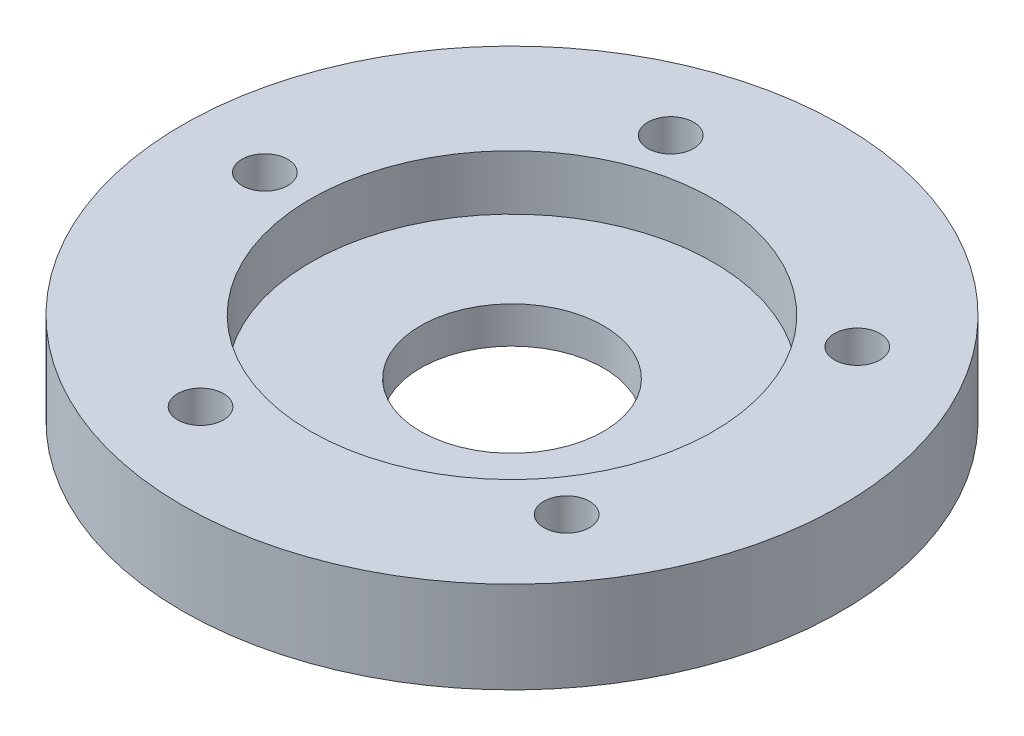
SolidWorks part; units mm, degrees
ref_plane "Front Plane" through (0, 0, 0) normal (0, 0, 1) x (1, 0, 0)
ref_plane "Top Plane" through (0, 0, 0) normal (0, 1, 0) x (1, 0, 0)
ref_plane "Right Plane" through (0, 0, 0) normal (1, 0, 0) x (0, 0, -1)
sketch "Sketch1" plane through (0, 0, 0) normal (0, 1, 0) x (1, 0, 0)
  line L0 (-13.5, 0) -> (13.5, 0) construction
  circle A0 centre (0, 0) radius 16
  circle A1 centre (0, 0) radius 13.5
  circle A2 centre (0, 0) radius 1.75
  circle A3 centre (-13.5, 0) radius 1.25
  circle A4 centre (-4.1717, 12.8393) radius 1.25
  circle A5 centre (10.9217, 7.9351) radius 1.25
  circle A6 centre (10.9217, -7.9351) radius 1.25
  circle A7 centre (-4.1717, -12.8393) radius 1.25
  point P19 (0, 0)
  dimension "D1" = 32
  dimension "D2" = 2.5
  dimension "D3" = 3.5
  dimension "D4" = 2.5
  dimension "D5" = 5
extrude "Boss-Extrude1" add sketch "Sketch1" along normal blind 2 and the other way blind 3 contours A0 A7 A1 A3 A4 A5 A6 | L0 A3 A1 A7 A6 A2 | A3 L0 A2 A1 A5 A4 region at (0, 0, -5.7653) region at (0, 0, 5.7653) region at (-15.5475, 0, 0)
sketch "Sketch2" plane through (0, 2, 0) normal (0, 1, 0) x (1, 0, 0)
  circle A0 centre (0, 0) radius 2.95
  circle A1 centre (0, 0) radius 4.95
  dimension "D1" = 5.9
  dimension "D2" = 2
extrude "Boss-Extrude3" add sketch "Sketch2" along normal blind 3 contours A1 A0 region at (-4.81, 2, 0)
sketch "Sketch4" plane through (0, 2, 0) normal (0, 1, 0) x (1, 0, 0)
  circle A0 centre (0, 0) radius 2
sketch "Sketch5" plane through (0, -3, 0) normal (0, -1, 0) x (1, 0, 0)
  circle A0 centre (0, 0) radius 3.5
  dimension "D1" = 7
extrude "Cut-Extrude2" cut sketch "Sketch5" against normal blind 4
sketch "Sketch6" plane through (0, 2, 0) normal (0, 1, 0) x (1, 0, 0)
  circle A0 centre (0, 0) radius 16
  circle A1 centre (0, 0) radius 18
  dimension "D1" = 2
extrude "Boss-Extrude4" add sketch "Sketch6" against normal blind 5
sketch "Sketch7" plane through (0, 2, 0) normal (0, 1, 0) x (1, 0, 0)
  circle A0 centre (0, 0) radius 11
  dimension "22" = 22
extrude "Cut-Extrude3" cut sketch "Sketch7" against normal blind 3 and the other way blind 10
sketch "Sketch8" plane through (0, -1, 0) normal (0, 1, 0) x (1, 0, 0)
  circle A0 centre (0, 0) radius 5
  dimension "D1" = 10
extrude "Cut-Extrude4" cut sketch "Sketch8" against normal blind 3
